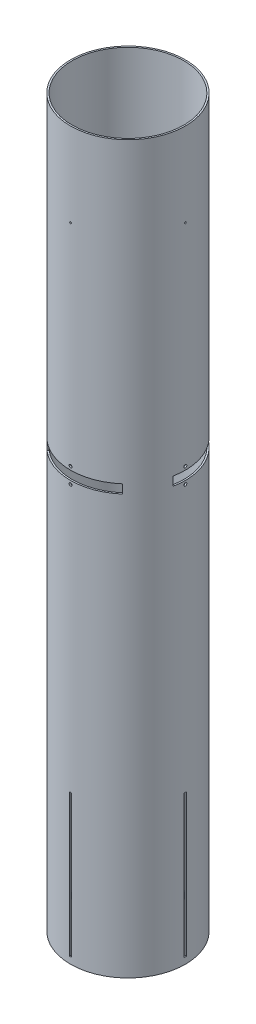
SolidWorks part; units mm, degrees
material "A-Glass Fiber"
ref_plane "Front Plane" through (0, 0, 0) normal (0, 0, 1) x (1, 0, 0)
ref_plane "Top Plane" through (0, 0, 0) normal (0, 1, 0) x (1, 0, 0)
ref_plane "Right Plane" through (0, 0, 0) normal (1, 0, 0) x (0, 0, -1)
sketch "Sketch1" plane through (0, 0, 0) normal (0, 1, 0) x (1, 0, 0)
  circle A0 centre (0, 0) radius 76.2
  circle A1 centre (0, 0) radius 78.359
  dimension "D1" = 152.4
  dimension "D2" = 156.718
extrude "Boss-Extrude1" add sketch "Sketch1" along normal blind 990.6
ref_plane "Plane1" through (0, 0, 0) normal (0.7071, 0, 0.7071) x (0.7071, 0, -0.7071)
ref_axis "Axis1" through (0, 990.6, 0) along (0, -1, 0)
sketch "Sketch2" plane through (0, 0, 0) normal (1, 0, 0) x (0, 0, -1)
  line L0 (0, 0) -> (0, 8.89)
  line L1 (1.5875, 8.89) -> (-1.5875, 8.89)
  line L2 (1.5875, 8.89) -> (1.5875, 203.2)
  line L3 (1.5875, 203.2) -> (-1.5875, 203.2)
  line L4 (-1.5875, 8.89) -> (-1.5875, 203.2)
  line L5 (1.5875, 8.89) -> (-1.5875, 203.2) construction
  line L6 (1.5875, 203.2) -> (-1.5875, 8.89) construction
  line L7 (78.359, 990.6) -> (-78.359, 990.6) construction
  line L8 (78.359, 990.6) -> (-78.359, 990.6)
  line L9 (0, 990.6) -> (0, 588.645)
  line L10 (-78.359, 0) -> (78.359, 0) construction
  circle A0 centre (0, 588.645) radius 2
  circle A1 centre (0, 876.3) radius 1.0922
  point P0 (0, 106.045)
  dimension "D4" = 4
  dimension "D6" = 2.1844
  dimension "D1" = 3.175
  dimension "D2" = 194.31
  dimension "D5" = 588.645
  dimension "D3" = 203.2
  dimension "D7" = 114.3
extrude "Fin Slots" cut sketch "Sketch2" against normal through all contours L4 L1 L2 L3 region at (0, 106.045, 0)
pattern_circular "CirPattern1" count 4 over 360 about axis through (0, 0, 0) along (0, 1, 0) of "Fin Slots" reverse direction yes
extrude "Cut-Extrude2" cut sketch "Sketch2<3>" against normal through all contours A0 region at (0, 590.0192, -1.3742)
sketch "Sketch2<3>" plane through (0, 0, 0) normal (1, 0, 0) x (0, 0, -1) same geometry as "Sketch2"
pattern_circular "CirPattern2" count 4 over 360 about axis through (0, 990.6, 0) along (0, -1, 0) of "Cut-Extrude2"
sketch "Sketch3" plane through (0, 0, 0) normal (0.7071, 0, 0.7071) x (0.7071, 0, -0.7071)
  line L0 (0, 0) -> (0, 127) construction
  circle A0 centre (0, 127) radius 3.175
  dimension "D1" = 6.35
  dimension "D2" = 127
extrude "Cut-Extrude3" cut sketch "Sketch3" against normal through all
ref_plane "Plane3" through (0, 583.8825, 0) normal (0, 1, 0) x (1, 0, 0)
sketch "Sketch7" plane through (0, 583.8825, 0) normal (0, 1, 0) x (1, 0, 0)
  line L0 (0, 0) -> (-76.8534, -15.2871)
  line L1 (0, 0) -> (0, 93.232) construction
  line L2 (0, 0) -> (-25.1877, 74.2005)
  line L3 (-78.359, 0) -> (0, 0) construction
  arc A0 (-78.3335, 2) -> (-78.3335, -2) centre (0, 0) ccw construction
  circle A1 centre (0, 0) radius 76.2 construction
  circle A2 centre (0, 0) radius 78.359
  circle A3 centre (0, 0) radius 78.359
  circle A4 centre (0, 0) radius 76.2
  circle A5 centre (0, 0) radius 78.359 construction
  arc A6 (2, 78.3335) -> (-2, 78.3335) centre (0, 0) ccw construction
  arc A7 (-78.3335, 2) -> (-78.3335, -2) centre (0, 0) ccw
  arc A8 (2, 78.3335) -> (-2, 78.3335) centre (0, 0) ccw
  dimension "D1" = 82.5
  dimension "D3" = 11.25
  dimension "D2" = 0
extrude "Cut-Extrude4" cut sketch "Sketch7" against normal blind 12.065 contours A4 A3 L0 region at (-75.9984, 583.8825, 14.0521)
pattern_circular "CirPattern3" count 3 over 360 about axis through (0, 990.6, 0) along (0, -1, 0) of "Cut-Extrude4"
extrude "Shear Screw Holes" cut sketch "Sketch2<4>" against normal through all contours L9 A1 | L9 A1 region at (0, 876.3, -0.4635) region at (0, 876.3, 0.4635)
sketch "Sketch2<4>" plane through (0, 0, 0) normal (1, 0, 0) x (0, 0, -1) same geometry as "Sketch2"
pattern_circular "Shear Screw Pattern" count 4 over 360 about axis through (0, 990.6, 0) along (0, -1, 0) of "Shear Screw Holes"
pattern_linear "LPattern1" count 2 spacing 21.524 along (0, -1, 0) of "Cut-Extrude2", "CirPattern2"
equation "\"D1@Boss-Extrude1\" = \"Aft_Section_Length\""
equation "\"AB_Coupler_OD_Length\"= 1in"
equation "\"AB_Coupling_Section_Length\"= 0.375in"
equation "\"AB_Coupler_Length\"= \"AB_Coupler_OD_Length\" + \"AB_Coupling_Section_Length\" * 2"
equation "\"AB_Coupler_Num_Screws\"= 4"
equation "\"AB_Coupling_Screw_Diameter\"= 0.15748in"
equation "\"Aft_Section_Length\"= 39in"
equation "\"D4@Sketch2\"=\"AB_Coupling_Screw_Diameter\""
equation "\"D1@CirPattern2\"=\"AB_Coupler_Num_Screws\""
equation "\"Rail_Nut_From_Bottom\"= 5in"
equation "\"Rail_Nut_Diam\"= 0.25in"
equation "\"D1@Sketch3\"=\"Rail_Nut_Diam\""
equation "\"D2@Sketch3\"=\"Rail_Nut_From_Bottom\""
equation "\"AB_BKHD_Thickness\"= 0.375in"
equation "\"AB_Mount_From_Bottom\"= 23.175in"
equation "\"Cutout_Angle\"= 80"
equation "\"Shear_Screw_Diameter\"= 0.086in"
equation "\"D6@Sketch2\"=\"Shear_Screw_Diameter\""
equation "\"Shear_Screw_Coupler_Location\"= 4.5in"
equation "\"D7@Sketch2\"=\"Shear_Screw_Coupler_Location\""
equation "\"Bodytube_OD\"= 6.17in"
equation "\"Bodytube_ID\"= 5.998in"
equation "\"Motor_OD\"= 4in"
equation "\"Fwd_Tube_Length\"= 40in"
equation "\"Mid_Tube_Length\"= 1in"
equation "\"Mid_Coupler_Length\"= 13in"
equation "\"AB_Paddle_Height\"= 0.375in"
equation "\"Num_Cutouts\"= 3"
equation "\"AB_Coupler_OD\"= 6.17in"
equation "\"AB_Coupler_ID\"= 5.75in"
equation "\"AB_Coupler_Surface_Diameter\"= 5.998in"
equation "\"AB_Central_Bushing_Length\"= .4724in"
equation "\"Lead_Screw_Dist\"= 3.4in"
equation "\"Lead_Screw_Diam\"= 0.386in"
equation "\"Lead_Screw_Length\"= (\"Mid_Coupler_Length\" + 2*0.375in + 2*0.5in)"
equation "\"Paddle_Pin_Offset\"= .25in"
equation "\"Paddle_Pin_Radius\"= 2.25in"
equation "\"SS_Paddle_Pin_Radius\"= 2.25*0.66in"
equation "\"Paddle_Gear_OD\"= 3.2in"
equation "\"Drive_Gear_OD\"= 1.7in"
equation "\"Fwd_BKHD_From_Top\"= 18in"
equation "\"Fin_Thickness\"= .118in"
equation "\"Guiderail_Cutout_Diameter\"= 1.5in"
equation "\"DB9_Hole_Dist\"= 25mm"
equation "\"DB9_Relief_Width\"= 0.47in"
equation "\"DB9_Relief_Hole_Offset\"= 0.09in"
equation "\"Airbrakes_Wire_Hole_Dia\"= .25in"
equation "\"Airbrakes_Wire_Hole_Dist\"= 1.1in"
equation "\"Servo_Gear_Offset\"= 0.5in"
equation "\"D3@LPattern1\"=\"AB_Central_Bushing_Length\"+\"AB_Coupling_Section_Length\""
